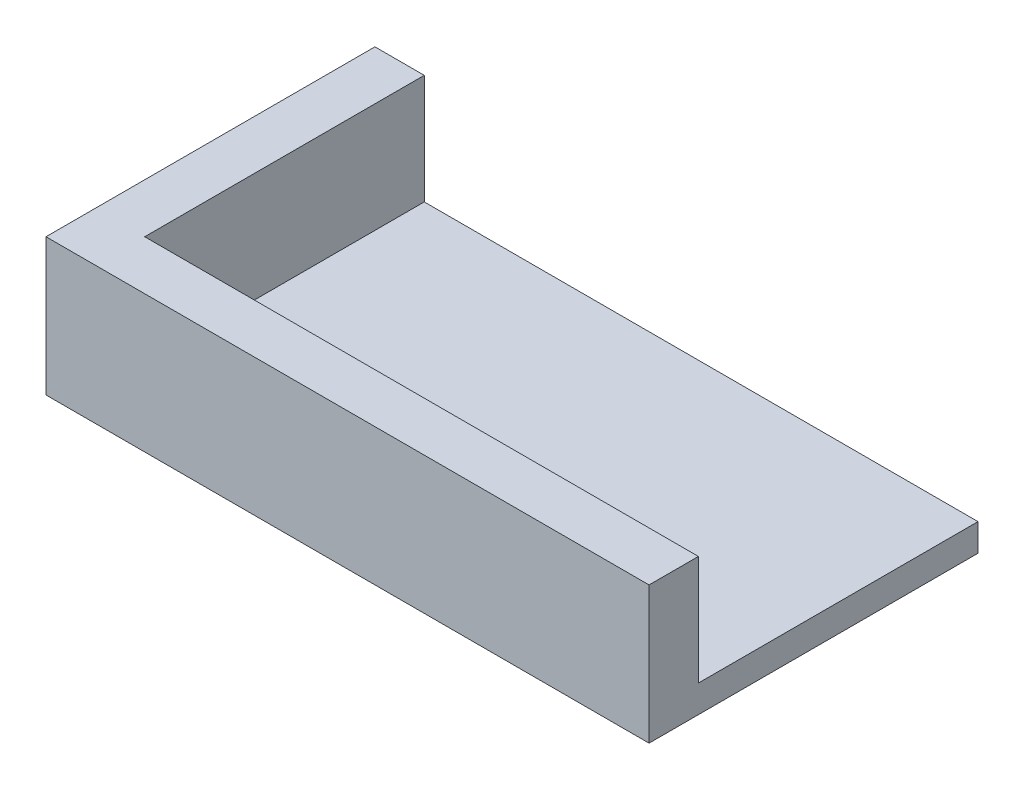
SolidWorks part; units mm, degrees
ref_plane "Front Plane" through (0, 0, 0) normal (0, 0, 1) x (1, 0, 0)
ref_plane "Top Plane" through (0, 0, 0) normal (0, 1, 0) x (1, 0, 0)
ref_plane "Right Plane" through (0, 0, 0) normal (1, 0, 0) x (0, 0, -1)
sketch "Sketch1" plane through (0, 0, 0) normal (0, 1, 0) x (1, 0, 0)
  line L0 (-69.85, -38.1) -> (69.85, -38.1)
  line L1 (-69.85, -38.1) -> (-69.85, 38.1)
  line L2 (69.85, -38.1) -> (69.85, 38.1)
  line L3 (-69.85, 38.1) -> (69.85, 38.1)
  line L4 (-69.85, -38.1) -> (69.85, 38.1) construction
  line L5 (69.85, -38.1) -> (-69.85, 38.1) construction
  line L10 (-58.42, -26.67) -> (58.42, 26.67) construction
  line L11 (58.42, -26.67) -> (-58.42, 26.67) construction
  point P1 (0, 0)
  point P2 (0, 0)
  dimension "D1" = 76.2
  dimension "D2" = 139.7
extrude "Boss-Extrude1" add sketch "Sketch1" along normal blind 31.75
sketch "Sketch2" plane through (0, 31.75, 0) normal (0, 1, 0) x (1, 0, 0)
  line L0 (-58.42, -26.67) -> (69.85, -26.67)
  line L1 (-58.42, -26.67) -> (-58.42, 38.1459)
  line L2 (69.85, -26.67) -> (69.85, 38.1459)
  line L3 (-58.42, 38.1459) -> (69.85, 38.1459)
  line L4 (69.85, -38.1) -> (69.85, 38.1) construction
  line L5 (-69.85, 38.1) -> (-69.85, -38.1) construction
  line L9 (-69.85, -38.1) -> (69.85, -38.1) construction
  dimension "D1" = 11.43
  dimension "D2" = 11.43
extrude "Cut-Extrude1" cut sketch "Sketch2" against normal blind 25.4
sketch "Sketch3" plane through (0, 6.35, 0) normal (0, 1, 0) x (1, 0, 0)
  line L0 (-58.42, -26.67) -> (-48.26, -26.67)
  line L1 (-58.42, -26.67) -> (-58.42, -16.51)
  line L2 (-48.26, -26.67) -> (-48.26, -16.51)
  line L3 (-58.42, -16.51) -> (-48.26, -16.51)
  line L4 (-58.42, -26.67) -> (69.85, -26.67) construction
  dimension "D1" = 10.16
  dimension "D2" = 10.16
extrude "Boss-Extrude3" add sketch "Sketch3" along normal blind 12.7
sketch "Sketch4" plane through (0, 19.05, 0) normal (0, 1, 0) x (1, 0, 0)
  line L0 (-48.26, -26.67) -> (-48.26, -16.51) construction
  line L1 (-48.26, -16.51) -> (-58.42, -16.51) construction
  circle A0 centre (-53.34, -21.59) radius 2.032
  point P4 (-48.26, -21.59)
  dimension "D1" = 4.064
  dimension "D2" = 5.08
  dimension "D3" = 5.08
extrude "Cut-Extrude2" cut sketch "Sketch4" against normal through all
sketch "Sketch5" plane through (0, 19.05, 0) normal (0, 1, 0) x (1, 0, 0)
  circle A0 centre (-53.34, -21.59) radius 3.937
extrude "Cut-Extrude3" cut sketch "Sketch5" against normal blind 2.286
